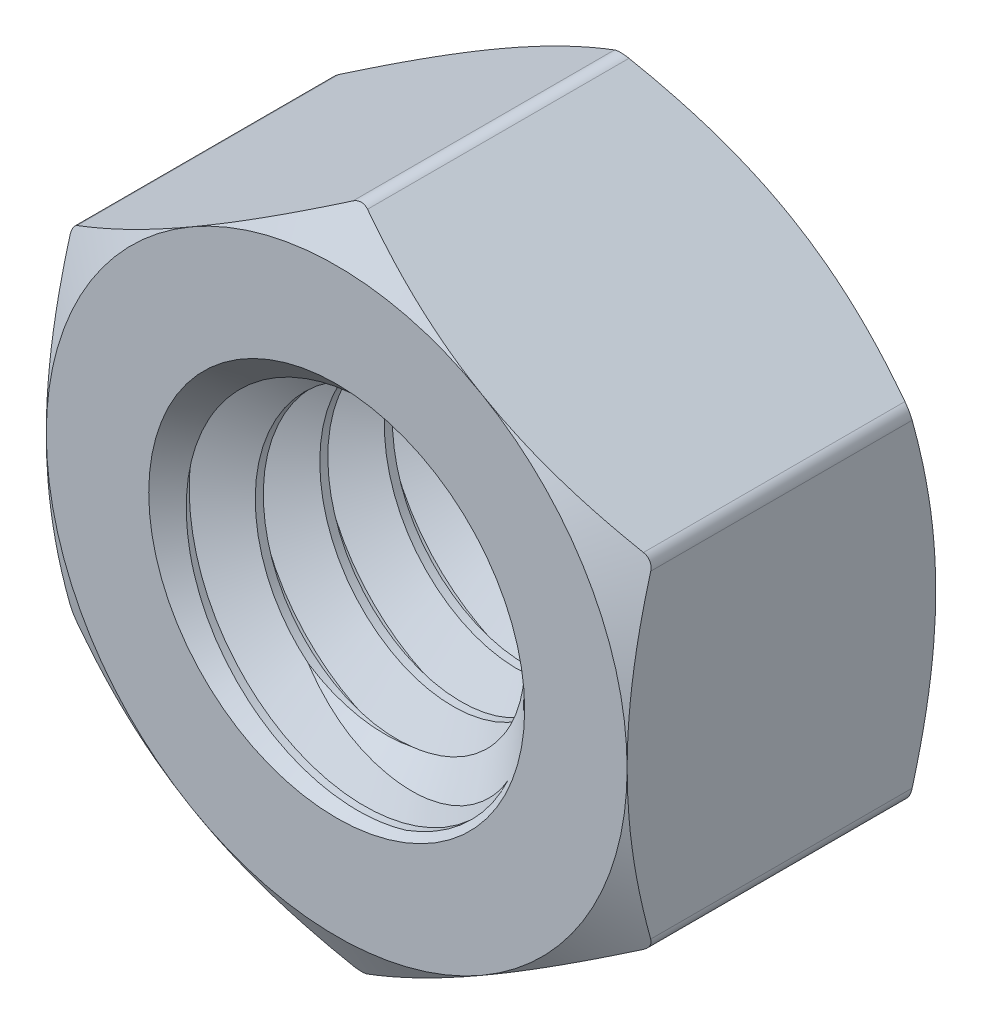
SolidWorks part; units mm, degrees
ref_plane "Front" through (0, 0, 0) normal (0, 0, 1) x (1, 0, 0)
ref_plane "Top" through (0, 0, 0) normal (0, 1, 0) x (1, 0, 0)
ref_plane "Right" through (0, 0, 0) normal (1, 0, 0) x (0, 0, -1)
sketch "Sketch1" plane through (0, 0, 0) normal (0, 0, 1) x (1, 0, 0)
  line L0 (0, 3.9688) -> (0, 2.5576) construction
  line L1 (-6.35, 3.6662) -> (-6.35, -3.6662)
  line L2 (-6.35, -3.6662) -> (0, -7.3323)
  line L3 (0, -7.3323) -> (6.35, -3.6662)
  line L4 (6.35, -3.6662) -> (6.35, 3.6662)
  line L5 (6.35, 3.6662) -> (0, 7.3323)
  line L6 (0, 7.3323) -> (-6.35, 3.6662)
  circle A0 centre (0, 0) radius 6.35 construction
  circle A1 centre (0, 0) radius 3.9688 construction
  point P10 (0, 3.9688)
  dimension "Width" = 12.7
  dimension "Thread Size" = 7.9375
  dimension "Thread Pitch" = 1.4111
sketch "Sketch2" plane through (0, 0, 0) normal (1, 0, 0) x (0, 0, -1)
  line L0 (-3.3734, 0) -> (3.3734, 0) construction
  line L1 (-3.3734, 7.3323) -> (3.3734, 7.3323) construction
  dimension "Height" = 6.7469
sketch "Sketch15" plane through (0, 0, 0) normal (0, 0, 1) x (1, 0, 0)
  line L1 (0, 7.3323) -> (-6.35, 3.6662)
  line L2 (-6.35, 3.6662) -> (-6.35, -3.6662)
  line L3 (-6.35, -3.6662) -> (0, -7.3323)
  line L4 (0, -7.3323) -> (6.35, -3.6662)
  line L5 (6.35, -3.6662) -> (6.35, 3.6662)
  line L6 (6.35, 3.6662) -> (0, 7.3323)
  circle A0 centre (0, 0) radius 6.35 construction
extrude "Boss-Extrude2" add sketch "Sketch15" along normal mid plane 6.7469
sketch "Sketch16" plane through (0, 0, 0) normal (0, 0, 1) x (1, 0, 0)
  circle A0 centre (0, 0) radius 3.9688 construction
  circle A1 centre (0, 0) radius 3.9688
sketch "Sketch4" plane through (0, 0, -3.3734) normal (0, 0, -1) x (-1, 0, 0)
  circle A0 centre (0, 0) radius 3.9688 construction
  circle A1 centre (0, 0) radius 3.9688
extrude "Cut-Extrude4" cut sketch "Sketch16" against normal through all both and the other way through all
sketch "Sketch7" plane through (0, 0, 3.3734) normal (0, 0, 1) x (1, 0, 0)
  circle A0 centre (0, 0) radius 6.35 construction
  circle A1 centre (0, 0) radius 6.35
extrude "Cut-Extrude5" cut sketch "Sketch7" against normal through all draft 60 flip side to cut
mirror "Mirror4" about plane through (0, 0, 0) normal (0, 0, 1) of "Cut-Extrude5"
fillet "Fillet2" radius 0.3175 6 edges at (-6.35, 3.6662, 0) (-6.35, -3.6662, 0) (0, -7.3323, 0) (6.35, -3.6662, 0) (6.35, 3.6662, 0) (0, 7.3323, 0)
sketch "Sketch8" plane through (0, 0, 3.3734) normal (0, 0, 1) x (1, 0, 0)
  line L0 (1.0272, -3.8335) -> (0, 0) construction
  line L2 (0, 3.9688) -> (0, 2.5576) construction
  circle A0 centre (0, 0) radius 3.9688 construction
  point P0 (1.0272, -3.8335)
  dimension "D1" = 15
sketch "Sketch13" plane through (0, 0, -3.3734) normal (0, 0, -1) x (-1, 0, 0)
  circle A0 centre (0, 0) radius 3.9688 construction
  circle A1 centre (0, 0) radius 3.9688
extrude "Boss-Extrude1" add sketch "Sketch13" against normal up to surface (6.7469 mm away) separate body up to face at (3.9688, 0, 3.3734)
curve "Helix/Spiral3" pitch 1.4111 height 8.158 radius 3.9688 centre (0, 0, -3.3734) axis (0, 0, 1) start towards (0, 1, 0)
sketch "Sketch12" plane through (0, 0, 0) normal (1, 0, 0) x (0, 0, -1)
  line L0 (4.6082, 3.9687) -> (3.3734, 3.9688)
  line L1 (4.6082, 3.9687) -> (4.079, 3.0522)
  line L2 (4.079, 3.0522) -> (3.9026, 3.0522)
  line L3 (3.9026, 3.0522) -> (3.3734, 3.9688)
  line L4 (3.9908, 3.0522) -> (3.9908, 3.9688) construction
  line L5 (3.638, 3.5105) -> (4.3436, 3.5105) construction
  dimension "D1" = 60
  dimension "D2" = 0.1764
  dimension "D3" = 0.7056
sweep "Cut-Sweep1" cut profiles "Sketch12" path "Helix/Spiral3" align with end faces yes
sketch "Sketch17" plane through (0, 0, 3.3734) normal (0, 0, 1) x (1, 0, 0)
  circle A1 centre (0, 0) radius 3.9688
  circle A2 centre (0, 0) radius 3.9688
  dimension "D1" = 0
extrude "Boss-Extrude3" add sketch "Sketch17" against normal up to surface (6.7469 mm away) up to face at (3.9688, 0, -3.3734)
combine bodies "Combine1" operation type subtract main body 127 bodies to subtract 118
sketch "Sketch10" plane through (0, 0, 3.3734) normal (0, 0, 1) x (1, 0, 0)
  circle A0 centre (0, 0) radius 3.9688 construction
  circle A1 centre (0, 0) radius 3.9688 construction
  circle A2 centre (0, 0) radius 4.1099
  dimension "D1" = 0.1411
extrude "Cut-Extrude2" cut sketch "Sketch10" against normal through all draft 45
sketch "Sketch11" plane through (0, 0, -3.3734) normal (0, 0, -1) x (-1, 0, 0)
  circle A1 centre (0, 0) radius 4.1099 construction
  circle A2 centre (0, 0) radius 4.1099
extrude "Cut-Extrude3" cut sketch "Sketch11" against normal through all draft 45
equation "\"D1\"= \"Height@Sketch2\""
equation "\"D3@Helix/Spiral3\"=\"Height@Sketch2\"+\"Thread Pitch@Sketch1\""
equation "\"D4@Helix/Spiral3\"=\"Thread Pitch@Sketch1\""
equation "\"D2@Sketch12\" = \"D4@Helix/Spiral3\"*.125"
equation "\"D3@Sketch12\" = \"D4@Helix/Spiral3\"*.50"
equation "\"D1@Boss-Extrude2\"=\"Height@Sketch2\""
equation "\"D1@Fillet2\"=\"Width@Sketch1\"*0.025"
equation "\"D1@Sketch10\"=\"Thread Pitch@Sketch1\"*0.1"
